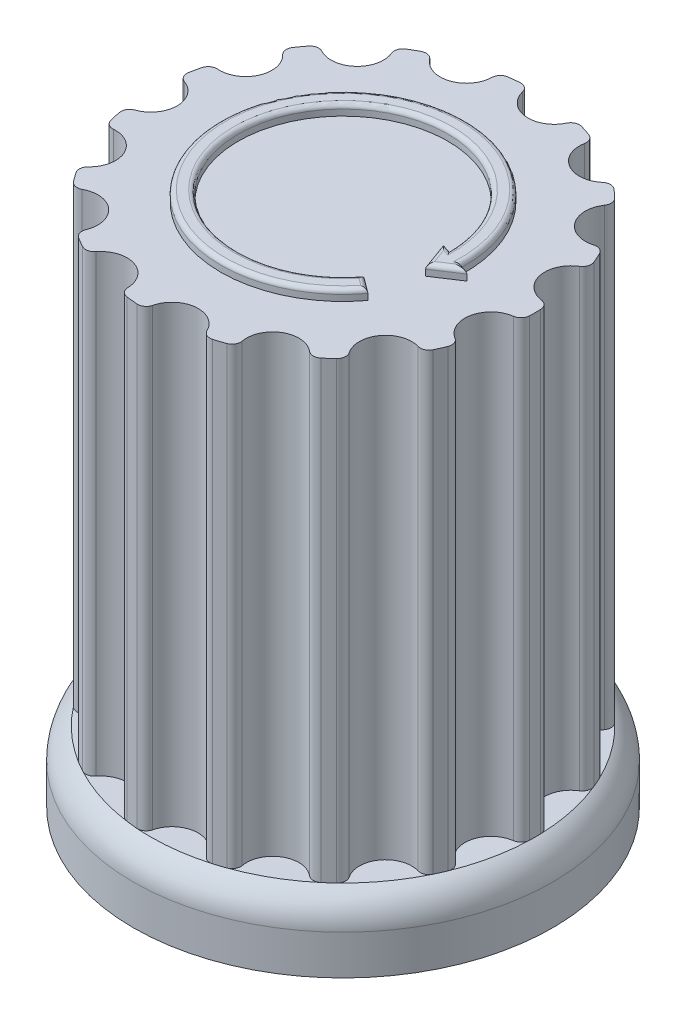
SolidWorks part; units mm, degrees
ref_plane "Front Plane" through (0, 0, 0) normal (0, 0, 1) x (1, 0, 0)
ref_plane "Top Plane" through (0, 0, 0) normal (0, 1, 0) x (1, 0, 0)
ref_plane "Right Plane" through (0, 0, 0) normal (1, 0, 0) x (0, 0, -1)
sketch "Sketch1" plane through (0, 0, 0) normal (0, 1, 0) x (1, 0, 0)
  circle A0 centre (0, 0) radius 6
extrude "Boss-Extrude1" add sketch "Sketch1" along normal blind 15
sketch "Sketch2" plane through (0, 15, 0) normal (0, 1, 0) x (1, 0, 0)
  circle A3 centre (0, 0) radius 5.5
  circle A4 centre (0, 0) radius 5.5
  circle M2 centre (0, 0) radius 6
  dimension "D1" = 0.5
extrude "Cut-Extrude1" cut sketch "Sketch2" against normal blind 13 contours A4 M2
fillet "Fillet1" radius 1 1 edges at (0, 2, 6)
sketch "Sketch3" plane through (0, 15, 0) normal (0, 1, 0) x (1, 0, 0)
  line L0 (-6.6, 0) -> (6.6, 0) construction
  circle A0 centre (-5.5, 0) radius 0.75
  circle A1 centre (0, 0) radius 5.5 construction
extrude "Cut-Extrude2" cut sketch "Sketch3" against normal blind 13
fillet "Fillet2" radius 0.25 2 edges at (-5.4489, 8.5, 0.7483) (-5.4489, 8.5, -0.7483)
pattern_circular "CirPattern1" count 15 every 24 about axis through (0, 0, 0) along (0, 1, 0) of "Cut-Extrude2", "Fillet2"
sketch "Sketch4" plane through (0, 0, 0) normal (0, -1, 0) x (1, 0, 0)
  line L1 (0, 0) -> (4.9165, -2.8385)
  line L2 (4.9165, -2.8385) -> (0, 0)
  line L3 (0, 0) -> (7.9027, 0)
  line L4 (6.6, 0) -> (-6.6, 0) construction
  circle A0 centre (0, 0) radius 3.5
  dimension "D1" = 30
extrude "Cut-Extrude3" cut sketch "Sketch4" against normal blind 14 contours A0
sketch "Sketch5" plane through (0, 14, 0) normal (0, -1, 0) x (1, 0, 0)
  line L0 (0, 0) -> (1.1, 0)
  line L1 (6.6, 0) -> (-6.6, 0) construction
  line L2 (1.1, 0) -> (-3.5, 0)
  line L3 (0, 0) -> (2.2365, -1.2912)
  line L4 (1.1, -3.3226) -> (1.1, 3.3226)
  line L7 (4.598, -2.366) -> (-4.348, 2.799)
  line L8 (4.348, -2.799) -> (-4.598, 2.366)
  circle A0 centre (0, 0) radius 3.5 construction
  circle A1 centre (0, 0) radius 3.5
  point P16 (1.1, 0)
  dimension "D1" = 30
  dimension "D2" = 0.5
  dimension "D3" = 4.6
extrude "Boss-Extrude2" add sketch "Sketch5" along normal blind 7
sketch "Sketch7" plane through (0, 15, 0) normal (0, 1, 0) x (1, 0, 0)
  line L0 (3, 0) -> (3.5, 0)
  line L1 (2.4033, -1.7955) -> (2.8039, -2.0948)
  line L2 (2.6036, -1.9452) -> (3.25, 0)
  line L3 (3.25, 0) -> (3.029, -0.6649)
  line L4 (3.029, -0.6649) -> (3.7394, -0.1981)
  line L5 (3.7394, -0.1981) -> (2.7394, 0.1342)
  line L6 (2.7394, 0.1342) -> (3.029, -0.6649)
  circle A0 centre (0, 0) radius 3.5
  circle A1 centre (0, 0) radius 3
  dimension "D1" = 0.5
  dimension "D2" = 1
  dimension "D3" = 0.85
  dimension "D4" = 0.85
extrude "Boss-Extrude4" add sketch "Sketch7" along normal blind 0.3 contours A1 L5 L0 A0 L1 | L4 A0 L5 L2 | L5 A0 L0 L3 | A0 L4 L5 | L5 L3 L0
fillet "Fillet5" radius 0.125 7 edges at (2.6036, 15.3, 1.9452) (-3.3024, 15.3, -1.1595) (3.6187, 15.3, 0.158) (3.3842, 15.3, 0.4315) (2.8842, 15.3, 0.2654) (2.8695, 15.3, -0.091) (-2.8544, 15.3, -0.9234)
